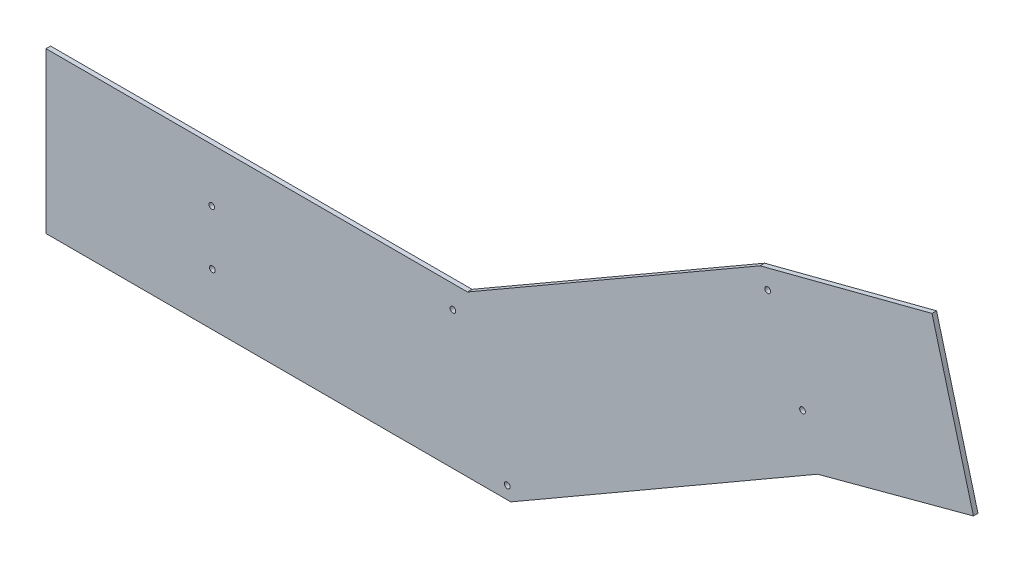
SolidWorks part; units mm, degrees
ref_plane "Plan de face" through (0, 0, 0) normal (0, 0, 1) x (1, 0, 0)
ref_plane "Plan de dessus" through (0, 0, 0) normal (0, 1, 0) x (1, 0, 0)
ref_plane "Plan de droite" through (0, 0, 0) normal (1, 0, 0) x (0, 0, -1)
sketch "Model" plane through (0, 0, 0) normal (0, 0, 1) x (1, 0, 0)
  line L0 (152.8114, 25.9717) -> (138.2826, 80.2215)
  line L1 (98.1506, 11.3316) -> (152.8114, 25.9717)
  line L2 (-9.3986, -50.8585) -> (98.1506, 11.3316)
  line L3 (-172.3739, -50.8585) -> (-9.3986, -50.8585)
  line L4 (-24.5886, 5.3017) -> (-172.3739, 5.2915)
  line L5 (138.2826, 80.2215) -> (78.0109, 64.5416)
  line L6 (-151.6088, 5.3124) -> (-151.6088, 5.2929)
  line L7 (-24.5886, 5.3017) -> (78.0109, 64.5416)
  line L8 (-172.3739, 5.3124) -> (-172.3739, -50.6876)
  line L9 (-172.3739, -50.6876) -> (-172.3739, -50.8585)
  circle A0 centre (80.6856, 58.4893) radius 1
  circle A1 centre (92.8776, 28.0855) radius 1
  circle A2 centre (-29.7028, -2.6485) radius 1
  circle A3 centre (-10.6528, -46.4381) radius 1
  circle A4 centre (-114.2594, -13.4181) radius 1
  circle A5 centre (-114.0308, -32.4935) radius 1
extrude "Boss.-Extru.1" add sketch "Model" along normal blind 1.6 contours L8 L9 L3 L2 L1 L0 L5 L7 L4 A5 A4 A3 A2 A1 A0 region at (-10.1589, 0.0699, 0)
